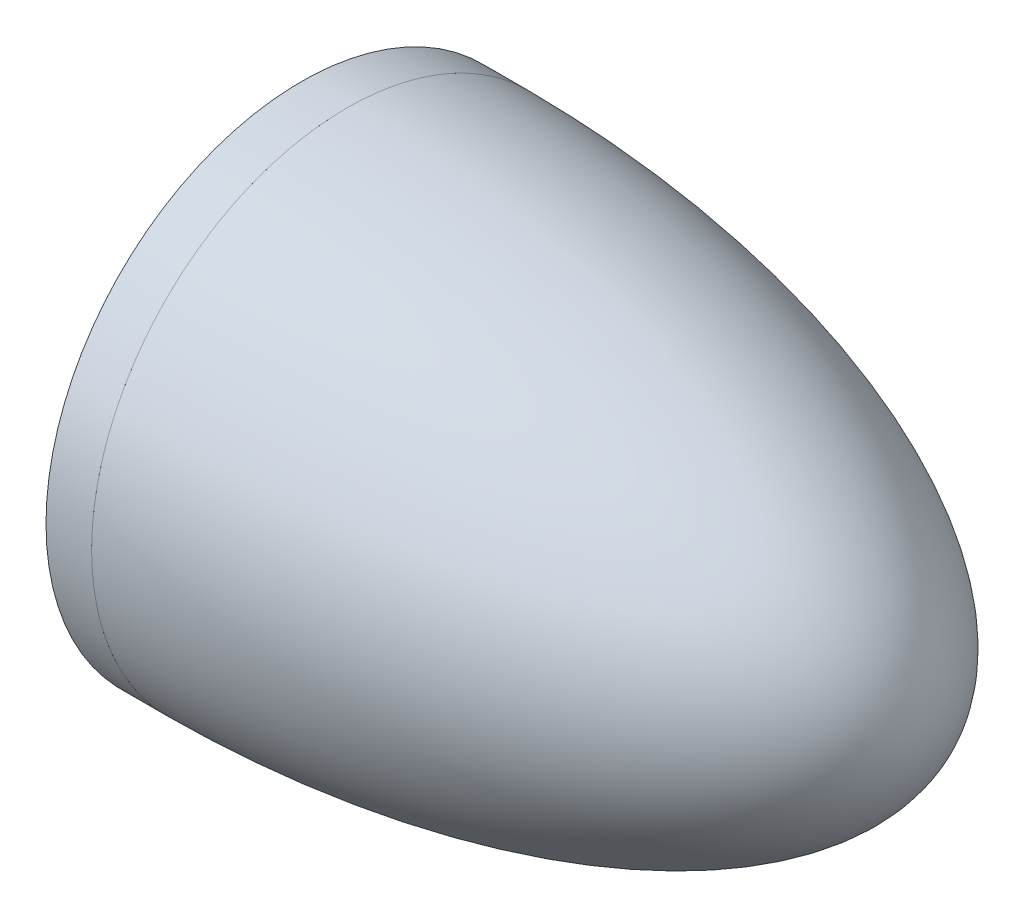
SolidWorks part; units mm, degrees
ref_plane "Front Plane" through (0, 0, 0) normal (0, 0, 1) x (1, 0, 0)
ref_plane "Top Plane" through (0, 0, 0) normal (0, 1, 0) x (1, 0, 0)
ref_plane "Right Plane" through (0, 0, 0) normal (1, 0, 0) x (0, 0, -1)
sketch "Sketch5" plane through (0, 0, 0) normal (0, 0, 1) x (1, 0, 0)
  line L0 (0, 0) -> (51.4986, 0) construction
  line L1 (-0.329, 27.94) -> (0, 0)
  line L2 (0, 0) -> (63.171, 0)
  spline S0 degree 4 poles (-6.683, 27.7999) (-6.4766, 27.8087) (-6.0715, 27.8255) (-5.3321, 27.8562) (-4.026, 27.8934) (-2.834, 27.924) (-1.0605, 27.9404) (0.0548, 27.9416) (1.5107, 27.9309) (2.6298, 27.9112) (3.8627, 27.8815) (5.0336, 27.842) (6.239, 27.7924) (7.424, 27.7329) (8.6198, 27.6634) (9.8088, 27.5837) (11.2978, 27.4714) (13.0811, 27.3163) (15.1599, 27.105) (17.5304, 26.8213) (19.8956, 26.4944) (22.8438, 26.0304) (26.3664, 25.3819) (29.8652, 24.6132) (33.3324, 23.7135) (36.7677, 22.7005) (40.166, 21.5674) (43.983, 20.0845) (47.6918, 18.3462) (50.7497, 16.6472) (53.1867, 15.0752) (55.1145, 13.6642) (56.8349, 12.2135) (58.2998, 10.7773) (59.5179, 9.3822) (60.4802, 8.0928) (61.2518, 6.8656) (61.8745, 5.6676) (62.3775, 4.4698) (62.7624, 3.2677) (63.0387, 1.9938) (63.1469, 0.995) (63.171, 0.3393) (63.171, 0) knots 0 0 0 0 0 0.009813 0.019627 0.039253 0.05888 0.078507 0.093261 0.108014 0.122768 0.137522 0.152275 0.167029 0.181783 0.196537 0.21129 0.226044 0.255551 0.285059 0.314566 0.344074 0.373581 0.432596 0.491611 0.521118 0.550625 0.60964 0.668655 0.723427 0.752934 0.782442 0.811949 0.841457 0.864083 0.883754 0.903425 0.920918 0.935669 0.95043 0.967579 0.983229 1 1 1 1 1 construction
  spline S1 degree 4 poles (-0.329, 27.94) (-0.054, 27.94) (0.5021, 27.9384) (1.5107, 27.9309) (2.6298, 27.9112) (3.8627, 27.8815) (5.0336, 27.842) (6.239, 27.7924) (7.424, 27.7329) (8.6198, 27.6634) (9.8088, 27.5837) (11.2978, 27.4714) (13.0811, 27.3163) (15.1599, 27.105) (17.5304, 26.8213) (19.8956, 26.4944) (22.8438, 26.0304) (26.3664, 25.3819) (29.8652, 24.6132) (33.3324, 23.7135) (36.7677, 22.7005) (40.166, 21.5674) (43.983, 20.0845) (47.6918, 18.3462) (50.7497, 16.6472) (53.1867, 15.0752) (55.1145, 13.6642) (56.8349, 12.2135) (58.2998, 10.7773) (59.5179, 9.3822) (60.4802, 8.0928) (61.2518, 6.8656) (61.8745, 5.6676) (62.3775, 4.4698) (62.7624, 3.2677) (63.0387, 1.9938) (63.1469, 0.995) (63.171, 0.3393) (63.171, 0) knots 0.078507 0.078507 0.078507 0.078507 0.078507 0.093261 0.108014 0.122768 0.137522 0.152275 0.167029 0.181783 0.196537 0.21129 0.226044 0.255551 0.285059 0.314566 0.344074 0.373581 0.432596 0.491611 0.521118 0.550625 0.60964 0.668655 0.723427 0.752934 0.782442 0.811949 0.841457 0.864083 0.883754 0.903425 0.920918 0.935669 0.95043 0.967579 0.983229 1 1 1 1 1
  point P7 (-17.9912, 52.8767)
revolve "Revolve1" add sketch "Sketch5" angle 360 about L0
sketch "Sketch6" plane through (0, 0, 0) normal (1, 0, 0) x (0, 0, -1)
  circle A0 centre (0, 0) radius 27.94
  dimension "D1" = 55.88
extrude "Boss-Extrude6" add sketch "Sketch6" against normal blind 5
sketch "Sketch7" plane through (-5, 0, 0) normal (-1, 0, 0) x (0, 0, 1)
  line L1 (-1.24, 1.27) -> (1.27, 1.27)
  line L2 (-1.24, 1.27) -> (-1.24, -1.24)
  line L3 (-1.24, -1.24) -> (1.27, -1.24)
  line L4 (1.27, 1.27) -> (1.27, -1.24)
  dimension "D1" = 2.51
  dimension "D2" = 2.51
  dimension "D3" = 1.27
  dimension "D4" = 1.27
extrude "Cut-Extrude2" cut sketch "Sketch7" against normal blind 4
